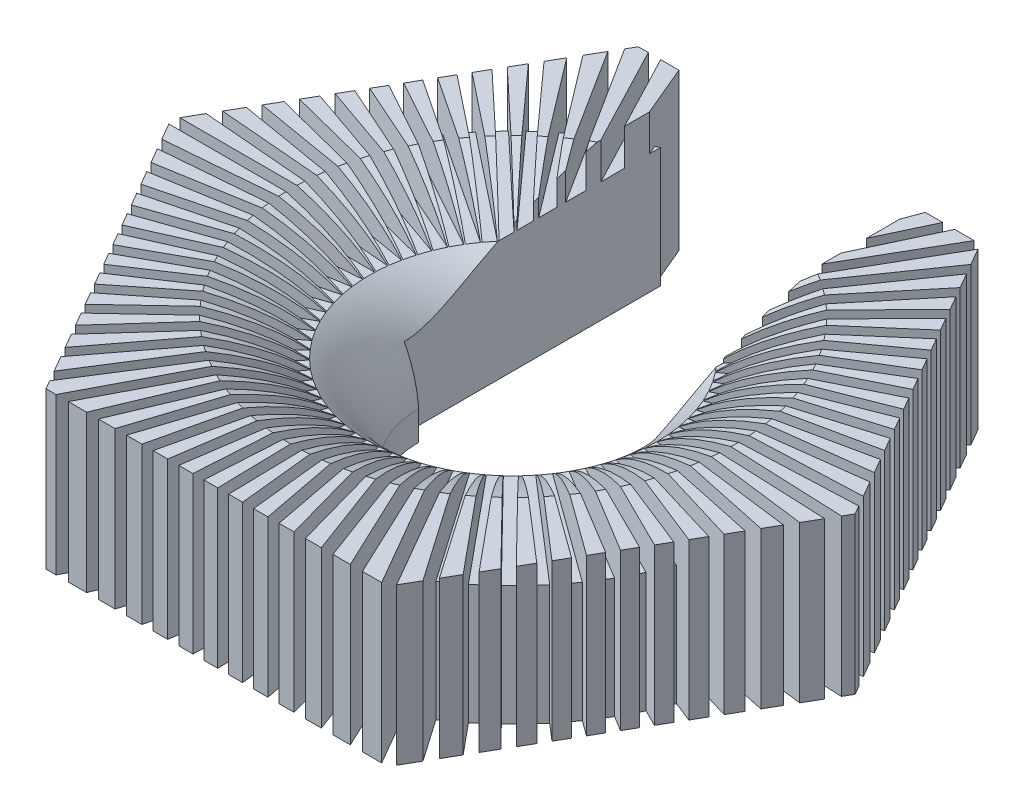
SolidWorks part; units mm, degrees
ref_plane "Front Plane" through (0, 0, 0) normal (0, 0, 1) x (1, 0, 0)
ref_plane "Top Plane" through (0, 0, 0) normal (0, 1, 0) x (1, 0, 0)
ref_plane "Right Plane" through (0, 0, 0) normal (1, 0, 0) x (0, 0, -1)
sketch "Sketch1" plane through (0, 0, 0) normal (0, 1, 0) x (1, 0, 0)
  line L1 (60.6218, 10) -> (38.9711, 47.5)
  line L2 (21.6506, 57.5) -> (-21.6506, 57.5)
  line L3 (-38.9711, 47.5) -> (-60.6218, 10)
  line L4 (-60.6218, -10) -> (-38.9711, -47.5)
  line L5 (-21.6506, -57.5) -> (21.6506, -57.5)
  line L6 (38.9711, -47.5) -> (60.6218, -10)
  circle A0 centre (0, 0) radius 57.5 construction
  arc A1 (-21.6506, -57.5) -> (-38.9711, -47.5) centre (-21.6506, -37.5) cw
  arc A2 (21.6506, -57.5) -> (38.9711, -47.5) centre (21.6506, -37.5) ccw
  arc A3 (60.6218, -10) -> (60.6218, 10) centre (43.3013, 0) ccw
  arc A4 (38.9711, 47.5) -> (21.6506, 57.5) centre (21.6506, 37.5) ccw
  arc A5 (-21.6506, 57.5) -> (-38.9711, 47.5) centre (-21.6506, 37.5) ccw
  arc A6 (-60.6218, -10) -> (-60.6218, 10) centre (-43.3013, 0) cw
  dimension "D1" = 115
  dimension "D2" = 20
extrude "Boss-Extrude2" add sketch "Sketch1" along normal blind 77.5
sketch "Sketch6" plane through (0, 77.5, 0) normal (0, 1, 0) x (1, 0, 0)
  circle A0 centre (0, 0) radius 13
extrude "Cut-Extrude1" cut sketch "Sketch6" against normal up to surface (77.5 mm away) up to face at (0, 0, 0)
sketch "Sketch7" plane through (0, 0, 0) normal (0, 0, 1) x (1, 0, 0)
  line L0 (0, 77.5) -> (0, 0) construction
  line L1 (-21.6506, 77.5) -> (21.6506, 77.5) construction
  line L2 (0, 77.5) -> (13, 77.5) construction
  line L3 (13, 77.5) -> (13, 60)
  line L4 (13, 77.5) -> (30.5, 77.5)
  line L5 (38.9711, 77.5) -> (21.6506, 77.5) construction
  line L6 (13, 0) -> (63.3013, 0) construction
  line L7 (38.9711, 0) -> (38.9711, 77.5) construction
  line L8 (64.9423, 77.5) -> (47.4423, 77.5)
  line L9 (64.9423, 77.5) -> (64.9423, 60)
  line L10 (13, 77.5) -> (-13, 77.5) construction
  line L11 (13, 77.5) -> (18.5176, 71.4317) construction
  spline S0 degree 2 poles (13, 60) (14.0037, 72.8919) (30.5, 77.5) knots 0 0 0 1 1 1
  spline S1 degree 2 poles (64.9423, 60) (63.9386, 72.8919) (47.4423, 77.5) knots 0 0 0 1 1 1
  dimension "D1" = 13
  dimension "D2" = 17.5
  dimension "D3" = 17.5
  dimension "D4" = 8.2017
revolve "Cut-Revolve1" cut sketch "Sketch7" angle 360 about L0
ref_plane "Plane1" through (0, 38.75, 0) normal (0, 1, 0) x (1, 0, 0)
sketch "Sketch8" plane through (0, 0, 0) normal (0, 0, 1) x (1, 0, 0)
  line L0 (-63.3013, 77.5) -> (-63.3013, 0)
  line L1 (-13.3013, 5) -> (-38.3013, 5) construction
  line L2 (-38.3013, 5) -> (-38.3013, 0)
  line L3 (-63.3013, 0) -> (-38.3013, 0)
  line L4 (-13.3013, 0) -> (-13.3013, 5) construction
  line L5 (-38.3013, 5) -> (-38.3013, 72.5)
  line L6 (63.25, 38.75) -> (-63.25, 38.75) construction
  line L7 (-63.3013, 38.75) -> (-38.3013, 38.75) construction
  line L8 (-13.3013, 77.5) -> (-13.3013, 72.5)
  line L9 (-63.3013, 77.5) -> (-13.3013, 77.5)
  line L10 (-13.3013, 72.5) -> (-38.3013, 72.5)
  line L11 (-38.3013, 0) -> (-13.3013, 0) construction
  point P3 (-66.188, 24)
  dimension "D1" = 50
  dimension "D2" = 50
  dimension "D3" = 5
  dimension "D4" = 25
extrude "Cut-Extrude2" cut sketch "Sketch8" against normal blind 0.75 and the other way blind 0.75
pattern_circular "CirPattern1" count 75 over 360 about axis through (0, 0, 0) along (0, 1, 0) of "Cut-Extrude2"
sketch "Sketch9" plane through (0, 77.5, 0) normal (0, 1, 0) x (1, 0, 0)
  line L1 (47.054, 0) -> (23.527, 40.75)
  line L2 (23.527, 40.75) -> (-23.527, 40.75)
  line L3 (-23.527, 40.75) -> (-47.054, 0)
  line L4 (-47.054, 0) -> (-23.527, -40.75)
  line L5 (-23.527, -40.75) -> (23.527, -40.75)
  line L6 (23.527, -40.75) -> (47.054, 0)
  circle A0 centre (0, 0) radius 40.75 construction
  dimension "D1" = 81.5
extrude "Cut-Extrude3" cut sketch "Sketch9" against normal blind 67 flip side to cut
sketch "Sketch11" plane through (0, 0, 0) normal (0, -1, 0) x (1, 0, 0)
  line L0 (15, 0) -> (-15, 0) construction
  line L1 (-15, 0) -> (15, 0)
  line L2 (-15, 0) -> (-15, -62.1427)
  line L3 (15, 0) -> (15, -62.1427)
  line L4 (-15, -62.1427) -> (15, -62.1427)
  point P7 (0, 0)
  dimension "D1" = 30
extrude "Cut-Extrude6" cut sketch "Sketch11" against normal through all
sketch "Sketch13" plane through (0, 0, 0) normal (0, -1, 0) x (1, 0, 0)
  line L1 (81.1275, 68.9387) -> (-81.1275, 68.9387)
  line L2 (81.1275, 68.9387) -> (81.1275, -68.9387)
  line L3 (81.1275, -68.9387) -> (-81.1275, -68.9387)
  line L4 (-81.1275, 68.9387) -> (-81.1275, -68.9387)
  line L5 (81.1275, 68.9387) -> (-81.1275, -68.9387) construction
  line L6 (81.1275, -68.9387) -> (-81.1275, 68.9387) construction
  point P0 (0, 0)
extrude "Cut-Extrude7" cut sketch "Sketch13" against normal blind 56
